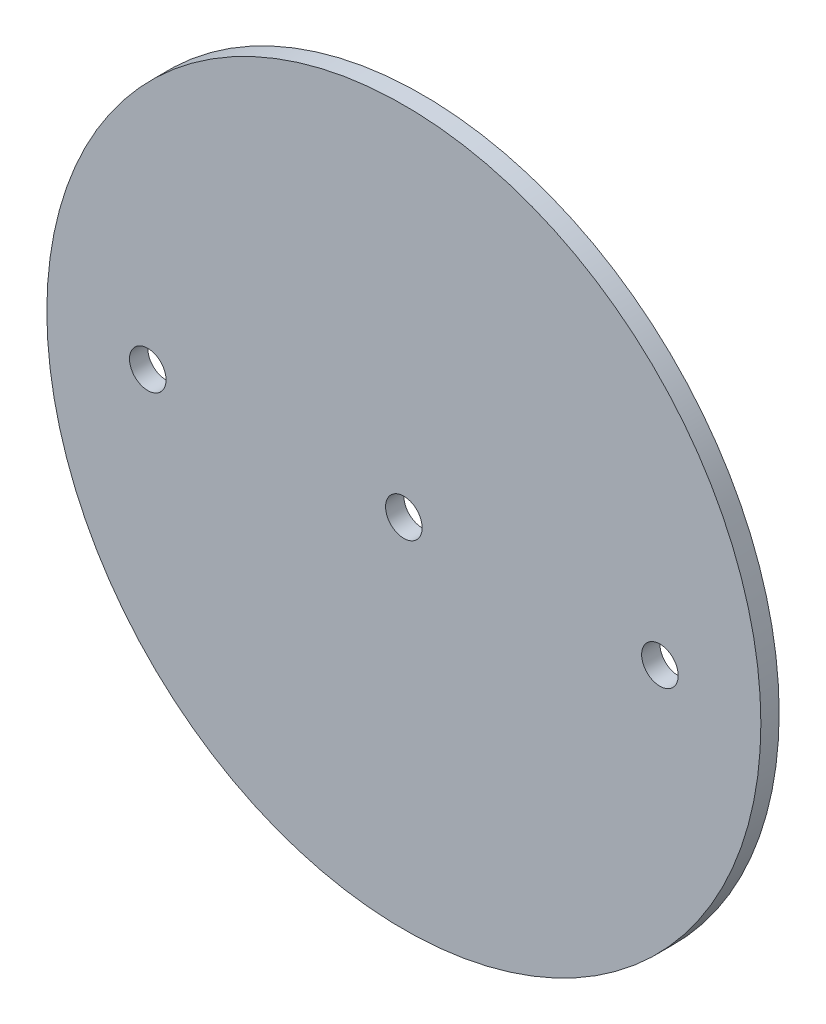
SolidWorks part; units mm, degrees
ref_plane "Front Plane" through (0, 0, 0) normal (0, 0, 1) x (1, 0, 0)
ref_plane "Top Plane" through (0, 0, 0) normal (0, 1, 0) x (1, 0, 0)
ref_plane "Right Plane" through (0, 0, 0) normal (1, 0, 0) x (0, 0, -1)
sketch "Sketch1" plane through (0, 0, 0) normal (0, 0, 1) x (1, 0, 0)
  circle A0 centre (0, 0) radius 61.976
  dimension "D1" = 123.952
extrude "Boss-Extrude1" add sketch "Sketch1" along normal mid plane 3.175
sketch "Sketch2" plane through (0, 0, 1.5875) normal (0, 0, 1) x (1, 0, 0)
  line L0 (-1000, 0) -> (49000, 0) construction
  point P1 (0, 0)
  point P4 (44.45, 0)
  point P5 (-44.45, 0)
  dimension "D1" = 44.45
  dimension "D2" = 88.9
hole_wizard "1/4 (0.25) Diameter Hole1" positions "Sketch2" profile "Sketch3" hole size "1/4" standard "ANSI Inch" end condition through all
sketch "Sketch3" plane through (-44.45, 0, 1.5875) normal (1, 0, 0) x (0, -1, 0)
  line L0 (0, 0) -> (0, 3.175)
  line L1 (0, 3.175) -> (3.175, 3.175)
  line L2 (3.175, 3.175) -> (3.175, 0)
  line L5 (3.175, 0) -> (0, 0)
  line L11 (0, -6.35) -> (0, 107.95) construction
  dimension "Thru Hole Dia." = 6.35
  dimension "Thru Hole Depth" = 3.175
equation "\"AIRFRAME_OD\"= 5.15in"
equation "\"AIRFRAME_ID\"= 5.00in"
equation "\"FLAT_T\"= 0.125in"
equation "\"NOSE_EXP_L\"= 27in"
equation "\"NOSE_SHOULDER_L\"= 5in"
equation "\"MAIN_L\"= 30in"
equation "\"RECO_COUP_L\"= 10in"
equation "\"RECO_SWITCH_L\"= 2in"
equation "\"DROGUE_L\"= 20in"
equation "\"ATS_FORE_COUP_L\"= 5.5in"
equation "\"ATS_AFT_COUP_L\"= 4.5in"
equation "\"LOWER_L\"= 30in"
equation "\"FIN_N\"= 4"
equation "\"CR_AFT_X\"= 0.5in"
equation "\"CR_FORE_X\"= 9.25in"
equation "\"FIN_ROOT\"= 5in"
equation "\"FIN_X\"= 0.75in"
equation "\"MOTOR_OD\"= 3.091in"
equation "\"MOTOR_ID\"= 3.00in"
equation "\"COUPLER_OD\"= 4.998in"
equation "\"COUPLER_ID\"= 4.88in"
equation "\"D1@Sketch1\"=\"COUPLER_ID\""
equation "\"D1@Boss-Extrude1\"=\"FLAT_T\""
equation "\"RECO_ROD_X\"= 3.5in"
equation "\"ATS_ROD_X\"= 3in"
equation "\"D1@Sketch2\"=\"RECO_ROD_X\"*0.5"
equation "\"D2@Sketch2\"=\"RECO_ROD_X\""
equation "\"MOTOR_L\"= 14in"
equation "\"MOTOR_LOWER_X\"= 2in"
